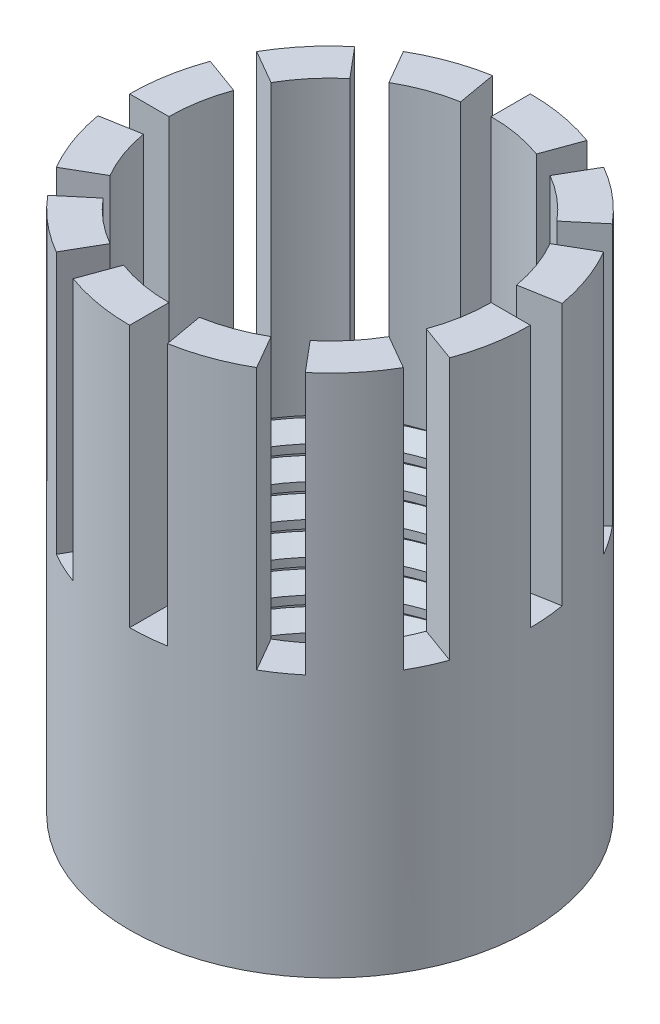
SolidWorks part; units mm, degrees
ref_plane "Front Plane" through (0, 0, 0) normal (0, 0, 1) x (1, 0, 0)
ref_plane "Top Plane" through (0, 0, 0) normal (0, 1, 0) x (1, 0, 0)
ref_plane "Right Plane" through (0, 0, 0) normal (1, 0, 0) x (0, 0, -1)
sketch "Sketch1" plane through (0, 0, 0) normal (1, 0, 0) x (0, 0, -1)
  line L0 (0, 0) -> (0, 20) construction
  line L1 (6.15, 0) -> (7.65, 0)
  line L2 (6.15, 0) -> (6.15, 20)
  line L3 (6.15, 20) -> (7.65, 20)
  line L4 (7.65, 0) -> (7.65, 20)
  point P7 (6.9, 20)
  dimension "D1" = 20
  dimension "D2" = 6.15
  dimension "D3" = 1.5
revolve "Revolve1" add sketch "Sketch1" angle 360 about L0
thread "Thread1" pitch 1.25 method cut profile "Thread Profile1" start angle 0, offset 11, length 13, pitch 1.25, diameter 12.3
ref_plane "Plane1" through (-6.15, 9, 0) normal (0, 0, 1) x (-1, 0, 0)
sketch "Thread Profile1" plane through (-6.15, 9, 0) normal (0, 0, 1) x (-1, 0, 0)
  line L0 (0, 0) -> (0, 1.25) construction
  line L1 (0, 0) -> (0.6766, 0.3906)
  line L2 (0.6766, 0.3906) -> (0.6766, 0.5469)
  line L3 (0.6766, 0.5469) -> (0, 0.9375)
  line L4 (0.6766, 0.4687) -> (0, 0.4687) construction
  line L11 (0, 0) -> (0, 0.9375)
  point P2 (0, 0)
  dimension "Pitch" = 1.25
  dimension "Profile_Angle" = 60
  dimension "Profile_Land" = 0.1562
  dimension "Profile_Height" = 0.6766
sketch "Sketch4" plane through (0, 20, 0) normal (0, 1, 0) x (1, 0, 0)
  line L0 (0, 7.65) -> (0, 0) construction
  line L1 (-1.3284, 7.5338) -> (0, 0) construction
  line L2 (-1.3284, 7.5338) -> (-1.0679, 6.0566)
  line L3 (0, 7.65) -> (0, 6.15)
  arc A1 (0, 7.65) -> (-1.3284, 7.5338) centre (0, 0) ccw
  circle A2 centre (0, 0) radius 7.65 construction
  arc A3 (0, 6.15) -> (-1.0679, 6.0566) centre (0, 0) ccw
  circle A4 centre (0, 0) radius 6.15 construction
  dimension "D1" = 170
extrude "Cut-Extrude1" cut sketch "Sketch4" against normal blind 10
pattern_circular "CirPattern1" count 12 over 360 about axis through (0, 20, 0) along (0, -1, 0) of "Cut-Extrude1"
